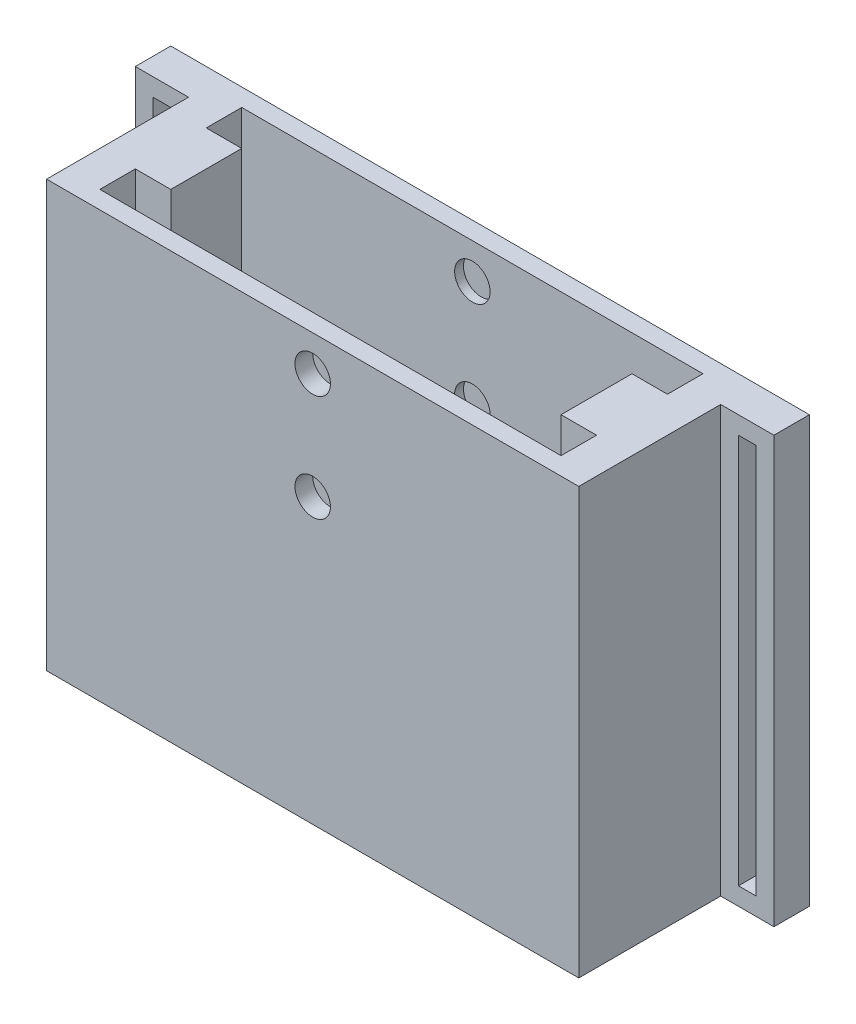
SolidWorks part; units mm, degrees
ref_plane "Front Plane" through (0, 0, 0) normal (0, 0, 1) x (1, 0, 0)
ref_plane "Top Plane" through (0, 0, 0) normal (0, 1, 0) x (1, 0, 0)
ref_plane "Right Plane" through (0, 0, 0) normal (1, 0, 0) x (0, 0, -1)
sketch "Sketch1" plane through (0, 0, 0) normal (0, 0, 1) x (1, 0, 0)
  line L1 (-75, 120) -> (75, 120)
  line L2 (-75, 120) -> (-75, 0)
  line L3 (-75, 0) -> (75, 0)
  line L4 (75, 120) -> (75, 0)
  point P4 (0, 0)
  dimension "D1" = 120
  dimension "D2" = 150
extrude "body" add sketch "Sketch1" along normal blind 50
sketch "Sketch2" plane through (0, 120, 0) normal (0, 1, 0) x (1, 0, 0)
  line L0 (-75, -25) -> (75, -25) construction
  line L1 (-75, -50) -> (-75, 0) construction
  line L2 (75, -50) -> (75, 0) construction
  line L3 (0, -50) -> (0, 0) construction
  line L4 (75, -50) -> (-75, -50) construction
  line L5 (-65, -5) -> (-65, -15)
  line L6 (-65, -15) -> (-55, -15)
  line L7 (-55, -15) -> (-55, -35)
  line L8 (-55, -35) -> (-65, -35)
  line L9 (-65, -35) -> (-65, -45)
  line L10 (-65, -45) -> (65, -45)
  line L11 (-65, -5) -> (65, -5)
  line L12 (65, -35) -> (65, -45)
  line L13 (55, -35) -> (65, -35)
  line L14 (55, -15) -> (55, -35)
  line L15 (65, -15) -> (55, -15)
  line L16 (65, -5) -> (65, -15)
  point P21 (0, -45)
  point P26 (0, -5)
  dimension "D1" = 10
  dimension "D2" = 10
  dimension "D3" = 130
  dimension "D4" = 40
extrude "spine socket " cut sketch "Sketch2" against normal through all
sketch "Sketch3" plane through (0, 0, 50) normal (0, 0, 1) x (1, 0, 0)
  circle A0 centre (0, 110) radius 5
  circle A1 centre (0, 80) radius 5
  dimension "D1" = 10
  dimension "D2" = 80
  dimension "D3" = 30
extrude "Cut-Extrude2" cut sketch "Sketch3" against normal offset from surface (47.5 mm away) 2.5 up to face at (0, 60, 5) offset beyond the face yes
sketch "Sketch4" plane through (0, 0, 0) normal (0, 0, -1) x (-1, 0, 0)
  line L1 (-90, 120) -> (90, 120)
  line L2 (-90, 120) -> (-90, 0)
  line L3 (-90, 0) -> (90, 0)
  line L4 (90, 120) -> (90, 0)
  line L5 (75, 120) -> (75, 0) construction
  line L6 (-75, 0) -> (-75, 120) construction
  line L7 (75, 120) -> (75, 0)
  line L8 (-75, 0) -> (-75, 120)
  line L9 (-75, 120) -> (75, 120) construction
  line L10 (-85, 115) -> (-80, 115)
  line L11 (-85, 115) -> (-85, 5)
  line L12 (-85, 5) -> (-80, 5)
  line L13 (-80, 115) -> (-80, 5)
  line L14 (0, 120) -> (0, 0) construction
  line L15 (85, 5) -> (80, 5)
  line L16 (85, 115) -> (80, 115)
  line L17 (85, 115) -> (85, 5)
  line L18 (80, 115) -> (80, 5)
  point P4 (0, 0)
  point P21 (-85, 60)
  point P22 (-90, 60)
  line M5 (75, 0) -> (75, 120)
  line M7 (-75, 120) -> (-75, 0)
  dimension "D1" = 5
  dimension "D2" = 180
  dimension "D3" = 5
  dimension "D4" = 5
extrude "Boss-Extrude2" add sketch "Sketch4" against normal blind 10 contours L4 L1 L3 M5 | L2 L3 L1 M7 region at (82.5, 118.7907, 0) region at (-82.5, 118.7907, 0)
